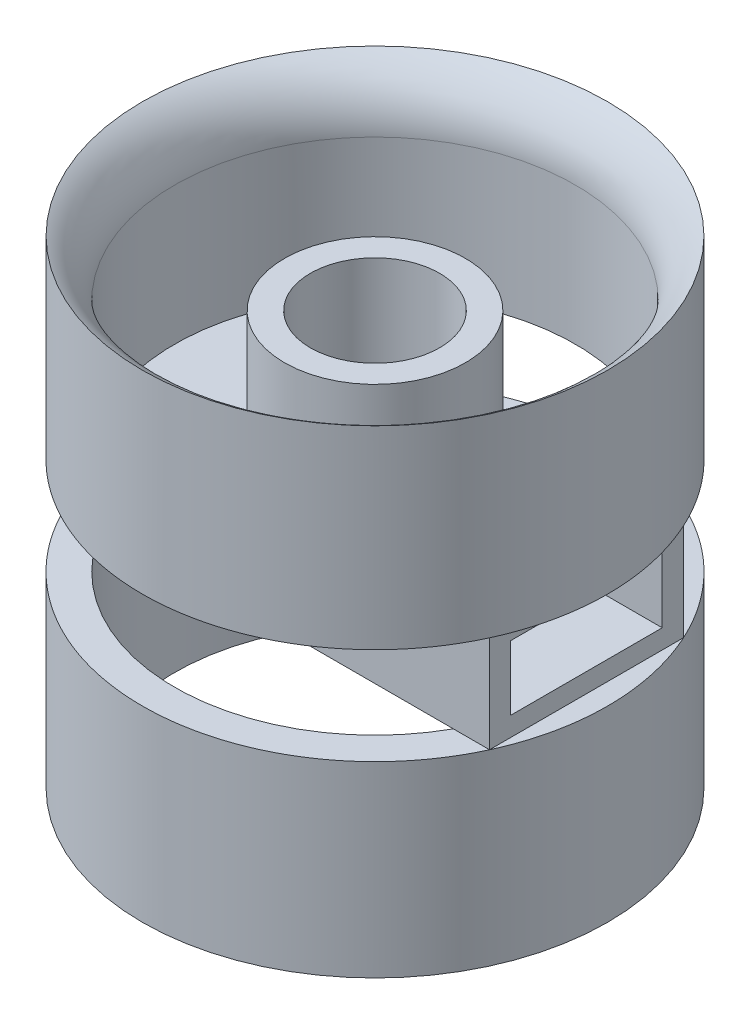
SolidWorks part; units mm, degrees
ref_plane "前基準面" through (0, 0, 0) normal (0, 0, 1) x (1, 0, 0)
ref_plane "上基準面" through (0, 0, 0) normal (0, 1, 0) x (1, 0, 0)
ref_plane "右基準面" through (0, 0, 0) normal (1, 0, 0) x (0, 0, -1)
sketch "草圖1" plane through (0, 0, 0) normal (0, 1, 0) x (1, 0, 0)
  circle A0 centre (0, 0) radius 36
  dimension "D1" = 72
extrude "填料-伸長1" add sketch "草圖1" along normal blind 30
sketch "草圖2" plane through (0, 30, 0) normal (0, 1, 0) x (1, 0, 0)
  circle A0 centre (0, 0) radius 31
  dimension "D1" = 62
extrude "除料-伸長1" cut sketch "草圖2" against normal blind 30
fillet "圓角1" radius 10 1 edges at (0, 30, 31)
sketch "草圖11" plane through (0, 0, 0) normal (0, 1, 0) x (1, 0, 0)
  line L0 (-1000, 0) -> (49000, 0) construction
  line L1 (0, -1000) -> (0, 49000) construction
  line L3 (-32.7237, 15) -> (32.7237, 15)
  line L4 (-32.7237, 15) -> (-32.7237, -15)
  line L5 (-32.7237, -15) -> (32.7237, -15)
  line L6 (32.7237, 15) -> (32.7237, -15)
  line L7 (-32.7237, 15) -> (32.7237, -15) construction
  line L8 (-32.7237, -15) -> (32.7237, 15) construction
  point P4 (0, 0)
  dimension "D1" = 30
extrude "填料-伸長8" add sketch "草圖11" against normal blind 15
sketch "草圖13" plane through (-32.7237, 0, 0) normal (-1, 0, 0) x (0, 0, 1)
  line L0 (0, -1000) -> (0, 49000) construction
  line L1 (-1000, 0) -> (49000, 0) construction
  line L2 (1.724, -7.0203) -> (49000, -7.0203) construction
  point P6 (1.724, -7.0203)
  point P8 (0, 0)
  point P9 (0, 0)
sketch "草圖16" plane through (-32.7237, 0, 0) normal (-1, 0, 0) x (0, 0, 1)
  line L0 (0, -201000) -> (0, 249000) construction
  line L1 (-11.725, -2.0203) -> (11.725, -2.0203)
  line L2 (-11.725, -2.0203) -> (-11.725, -12.0203)
  line L3 (-11.725, -12.0203) -> (11.725, -12.0203)
  line L4 (11.725, -2.0203) -> (11.725, -12.0203)
  line L5 (-11.725, -2.0203) -> (11.725, -12.0203) construction
  line L6 (-11.725, -12.0203) -> (11.725, -2.0203) construction
  line L7 (-199998.276, -7.0203) -> (249000, -7.0203) construction
  point P0 (0, -7.0203)
  dimension "D1" = 10
  dimension "D2" = 23.45
extrude "除料-伸長3" cut sketch "草圖16" against normal through all
sketch "草圖18" plane through (-32.7237, 0, 0) normal (-1, 0, 0) x (0, 0, 1)
  line L5 (-1011.725, -6.6247) -> (48988.275, -6.6247) construction
  line L10 (-1011.725, -7.6247) -> (48988.275, -7.6247) construction
sketch "草圖19" plane through (-32.7237, 0, 0) normal (-1, 0, 0) x (0, 0, 1)
  line L0 (-11.725, -6.6247) -> (-12.725, -6.6247)
  line L1 (-201011.725, -6.6247) -> (248988.275, -6.6247) construction
  line L2 (-11.725, -2.0203) -> (-11.725, -12.0203) construction
  line L3 (-12.725, -6.6247) -> (-12.725, -5.6247)
  line L4 (-12.725, -5.6247) -> (-13.725, -5.6247)
  line L5 (-13.725, -5.6247) -> (-13.725, -8.6248)
  line L6 (-13.725, -8.6248) -> (-12.725, -8.6248)
  line L7 (-12.725, -8.6248) -> (-12.725, -7.6247)
  line L8 (-201011.725, -7.6247) -> (248988.275, -7.6247) construction
  line L9 (-12.725, -7.6247) -> (-11.725, -7.6247)
  line L10 (-11.725, -7.6247) -> (-11.725, -6.6247)
extrude "除料-伸長4" cut sketch "草圖19" against normal blind 58
sketch "草圖21" plane through (0, 0, 0) normal (0, 1, 0) x (1, 0, 0)
  circle A0 centre (0, 0) radius 14
  dimension "D1" = 28
extrude "填料-伸長10" add sketch "草圖21" along normal blind 20
sketch "草圖22" plane through (0, 20, 0) normal (0, 1, 0) x (1, 0, 0)
  circle A0 centre (0, 0) radius 10
  dimension "D1" = 20
extrude "除料-伸長5" cut sketch "草圖22" against normal blind 20
sketch "草圖23" plane through (0, -15, 0) normal (0, -1, 0) x (1, 0, 0)
  circle A0 centre (0, 0) radius 36
  dimension "D1" = 72
extrude "填料-伸長11" add sketch "草圖23" along normal blind 29
sketch "草圖24" plane through (0, -44, 0) normal (0, -1, 0) x (1, 0, 0)
  circle A0 centre (0, 0) radius 31
  dimension "D1" = 62
extrude "除料-伸長7" cut sketch "草圖24" against normal blind 29
